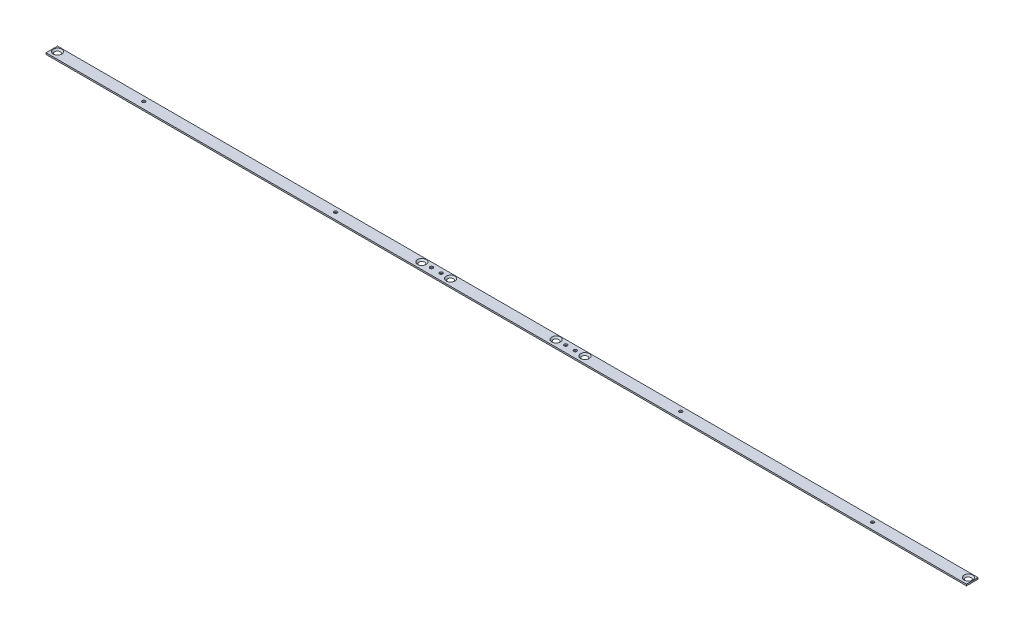
SolidWorks part; units mm, degrees
ref_plane "Front Plane" through (0, 0, 0) normal (0, 0, 1) x (1, 0, 0)
ref_plane "Top Plane" through (0, 0, 0) normal (0, 1, 0) x (1, 0, 0)
ref_plane "Right Plane" through (0, 0, 0) normal (1, 0, 0) x (0, 0, -1)
sketch "Sketch1" plane through (0, 0, 0) normal (0, 1, 0) x (1, 0, 0)
  line L1 (-480, -6) -> (480, -6)
  line L2 (-480, -6) -> (-480, 6)
  line L3 (-480, 6) -> (480, 6)
  line L4 (480, -6) -> (480, 6)
  line L5 (-480, -6) -> (480, 6) construction
  line L6 (-480, 6) -> (480, -6) construction
  point P0 (0, 0)
  dimension "D1" = 960
  dimension "D2" = 12
extrude "Boss-Extrude1" add sketch "Sketch1" along normal blind 1.5875
hole_wizard "CSK for M4 SFHCS1" positions "Sketch2" profile "Sketch3" countersink size "M4" standard "ANSI Metric" end condition through all
sketch "Sketch2" plane through (0, 1.5875, 0) normal (0, 1, 0) x (1, 0, 0)
  line L2 (-95, 1) -> (-65, 1)
  line L4 (45, 1) -> (75, 1)
  line L5 (480, 6) -> (-480, 6) construction
  line L6 (-480, 6) -> (-480, -6) construction
  point P7 (475, 1)
  point P9 (-95, 1)
  point P10 (-65, 1)
  point P14 (-80, 1)
  point P15 (45, 1)
  point P16 (75, 1)
  point P22 (60, 1)
  point P25 (-475, 1)
  dimension "D1" = 395
  dimension "D2" = 5
  dimension "D3" = 30
  dimension "D4" = 140
  dimension "D5" = 30
  dimension "D6" = 5
  dimension "D7" = 5
  dimension "D8" = 5
sketch "Sketch3" plane through (475, 1.5875, -1) normal (1, 0, 0) x (0, 0, 1)
  line L0 (0, 0) -> (0, 1.5875)
  line L1 (0, 1.5875) -> (2.25, 1.5875)
  line L2 (2.25, 1.5875) -> (2.25, 2.23)
  line L3 (2.25, 2.23) -> (4.48, 0)
  line L5 (4.48, 0) -> (0, 0)
  line L6 (-2.25, 2.23) -> (-4.48, 0) construction
  line L11 (0, -6.35) -> (0, 107.95) construction
  dimension "Thru Hole Dia." = 4.5
  dimension "Thru Hole Depth" = 1.5875
  dimension "Near C'Sink Dia." = 8.96
  dimension "Near C'Sink Angle" = 90
hole_wizard "M4x0.7 Tapped Hole2" positions "Sketch4" profile "Sketch6" tap size "M4x0.7" standard "ANSI Metric" end condition through all
sketch "Sketch4" plane through (0, 1.5875, 0) normal (0, 1, 0) x (1, 0, 0)
  line L3 (-85, 1) -> (-75, 1)
  line L5 (480, 6) -> (-480, 6) construction
  line L6 (55, 1) -> (65, 1)
  line L7 (475, 1) -> (75, 1)
  line L9 (175, 1) -> (375, 1)
  line L10 (-385, 1) -> (-185, 1)
  line L11 (-475, 1) -> (-95, 1)
  circle A0 centre (-95, 1) radius 4.48 construction
  circle A1 centre (45, 1) radius 4.48 construction
  point P1 (-85, 1)
  point P2 (-75, 1)
  point P6 (55, 1)
  point P7 (65, 1)
  point P43 (175, 1)
  point P44 (375, 1)
  point P47 (275, 1)
  point P48 (275, 1)
  point P54 (-385, 1)
  point P55 (-185, 1)
  point P69 (-285, 1)
  point P70 (-285, 1)
  dimension "D7" = 200
  dimension "D1" = 10
  dimension "D2" = 10
  dimension "D3" = 10
  dimension "D4" = 10
  dimension "D5" = 5
  dimension "D6" = 5
  dimension "D8" = 200
sketch "Sketch6" plane through (-85, 1.5875, -1) normal (1, 0, 0) x (0, 0, 1)
  line L0 (0, 0) -> (0, 1.5875)
  line L1 (0, 1.5875) -> (1.65, 1.5875)
  line L2 (1.65, 1.5875) -> (1.65, 0)
  line L5 (1.65, 0) -> (0, 0)
  line L11 (0, -6.35) -> (0, 107.95) construction
  dimension "Thru Tap Drill Dia." = 3.3
  dimension "Thru Tap Drill Depth" = 1.5875
cosmetic thread "Hole Thread3"
cosmetic thread "Hole Thread4"
cosmetic thread "Hole Thread5"
cosmetic thread "Hole Thread6"
cosmetic thread "Hole Thread7"
cosmetic thread "Hole Thread8"
cosmetic thread "Hole Thread9"
cosmetic thread "Hole Thread10"
